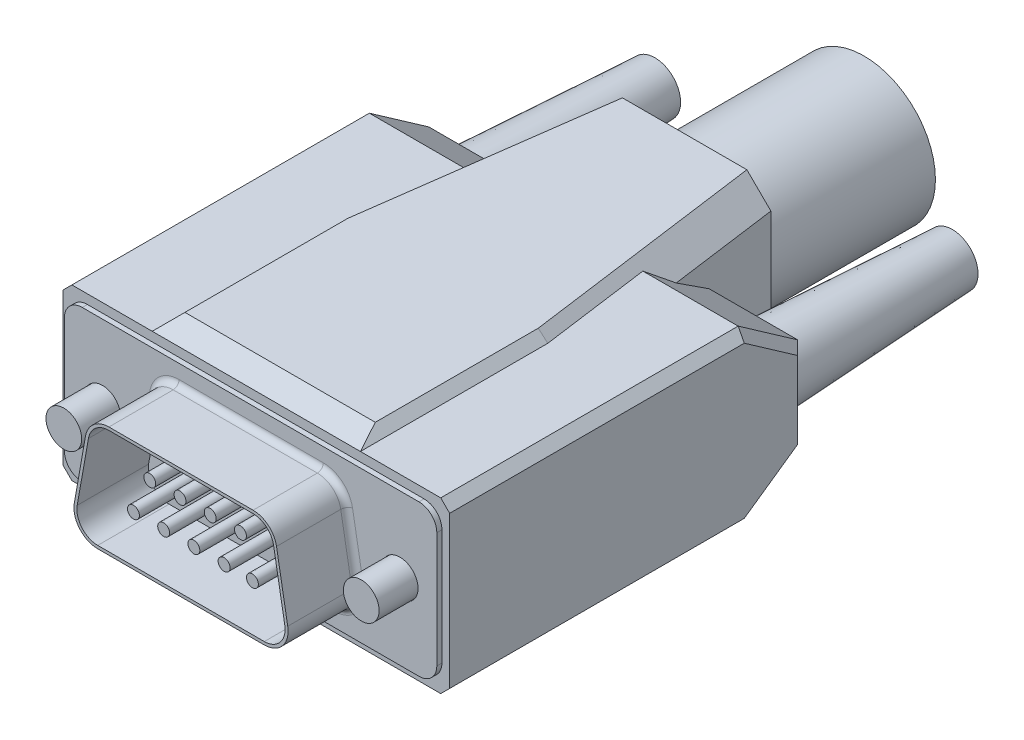
SolidWorks part; units mm, degrees
ref_plane "Plane1" through (0, 0, 0) normal (0, 0, 1) x (1, 0, 0)
ref_plane "Plane2" through (0, 0, 0) normal (0, 1, 0) x (1, 0, 0)
ref_plane "Plane3" through (0, 0, 0) normal (1, 0, 0) x (0, 0, -1)
other "Configuration Table"
sketch "Sketch1" plane through (0, 0, 0) normal (0, 0, 1) x (1, 0, 0)
  line L0 (-15.7, -6.35) -> (15.6, -6.35)
  line L1 (-15.7, -6.35) -> (-15.7, 6.35)
  line L2 (15.6, 6.35) -> (-15.7, 6.35)
  line L3 (15.6, 6.35) -> (15.6, -6.35)
  line L8 (-29.9573, 0) -> (30.1121, 0) construction
  line L9 (0, 20.0131) -> (0, -19.9874) construction
  circle A0 centre (12.5, 0) radius 1.525
  circle A1 centre (-12.5, 0) radius 1.525
  dimension "D10" = 3.05
  dimension "D1" = 12.7
  dimension "D2" = 31.3
  dimension "D5" = 12.5
  dimension "D6" = 15.6
  dimension "D7" = 6.35
extrude "Base-Extrude" add sketch "Sketch1" along normal mid plane 0.43
fillet "Fillet6" radius 1.5 4 edges at (15.6, 6.35, 0) (15.6, -6.35, 0) (-15.7, -6.35, 0) (-15.7, 6.35, 0)
sketch "Sketch4" plane through (0, 0, 0.215) normal (0, 0, 1) x (1, 0, 0)
  line L0 (20.0414, 0) -> (-20.2241, 0) construction
  line L1 (0, -10.1349) -> (0, 10.0435) construction
  line L2 (7, -4.67) -> (-7, -4.67)
  line L3 (-8.9696, -2.3227) -> (-8.028, 3.0173)
  line L4 (-6.0584, 4.67) -> (6.0584, 4.67)
  line L5 (8.9696, -2.3227) -> (8.028, 3.0173)
  arc A0 (-8.9696, -2.3227) -> (-7, -4.67) centre (-7, -2.67) ccw
  arc A1 (-6.0584, 4.67) -> (-8.028, 3.0173) centre (-6.0584, 2.67) ccw
  arc A2 (8.9696, -2.3227) -> (7, -4.67) centre (7, -2.67) cw
  arc A3 (6.0584, 4.67) -> (8.028, 3.0173) centre (6.0584, 2.67) cw
  point P15 (0, -4.67)
  point P18 (0, 4.67)
  dimension "D1" = 2
  dimension "D2" = 2
  dimension "D3" = 7
  dimension "D4" = 2.67
  dimension "D5" = 9.34
  dimension "D6" = 100
extrude "Boss-Extrude2" add sketch "Sketch4" along normal blind 5.9
fillet "Fillet8" radius 0.5 8 edges at (7.344, 4.2021, 0.215) (0, 4.67, 0.215) (8.4988, 0.3473, 0.215) (8.5321, -3.9556, 0.215) (0, -4.67, 0.215) (-8.5321, -3.9556, 0.215) (-8.4988, 0.3473, 0.215) (-7.344, 4.2021, 0.215)
sketch "Sketch5" plane through (0, 0, 6.115) normal (0, 0, 1) x (1, 0, 0)
  line L4 (-7, -4.42) -> (7, -4.42)
  line L5 (8.7234, -2.3661) -> (7.7818, 2.9739)
  line L6 (6.0584, 4.42) -> (-6.0584, 4.42)
  line L7 (-7.7818, 2.9739) -> (-8.7234, -2.3661)
  line L8 (-7, -4.42) -> (7, -4.42)
  line L9 (8.7234, -2.3661) -> (7.7818, 2.9739)
  line L10 (6.0584, 4.42) -> (-6.0584, 4.42)
  line L11 (-7.7818, 2.9739) -> (-8.7234, -2.3661)
  arc A4 (-8.7234, -2.3661) -> (-7, -4.42) centre (-7, -2.67) ccw
  arc A5 (7, -4.42) -> (8.7234, -2.3661) centre (7, -2.67) ccw
  arc A6 (7.7818, 2.9739) -> (6.0584, 4.42) centre (6.0584, 2.67) ccw
  arc A7 (-6.0584, 4.42) -> (-7.7818, 2.9739) centre (-6.0584, 2.67) ccw
  arc A8 (-8.7234, -2.3661) -> (-7, -4.42) centre (-7, -2.67) ccw
  arc A9 (7, -4.42) -> (8.7234, -2.3661) centre (7, -2.67) ccw
  arc A10 (7.7818, 2.9739) -> (6.0584, 4.42) centre (6.0584, 2.67) ccw
  arc A11 (-6.0584, 4.42) -> (-7.7818, 2.9739) centre (-6.0584, 2.67) ccw
  dimension "D1" = 0.25
extrude "Cut-Extrude1" cut sketch "Sketch5" against normal blind 6
sketch "Sketch8" plane through (0, 0, 0.115) normal (0, 0, 1) x (1, 0, 0)
  line L0 (-17.0623, 0) -> (18.229, 0) construction
  line L1 (0, 8.3424) -> (0, -9.7837) construction
  circle A0 centre (-5, -1.5) radius 0.5
  circle A1 centre (-3.625, 1.5) radius 0.5
  dimension "D1" = 1
  dimension "D4" = 3
  dimension "D3" = 1
  dimension "D2" = 5
  dimension "D5" = 1.375
  dimension "D6" = 1.5
extrude "Boss-Extrude3" add sketch "Sketch8" along normal blind 5
pattern_linear "LPattern1" count 4 spacing 2.54 along (1, 0, 0) of "Boss-Extrude3"
sketch "Sketch9" plane through (0, 0, -0.215) normal (0, 0, -1) x (-1, 0, 0)
  line L1 (-16.25, 7.125) -> (16.25, 7.125)
  line L2 (-16.25, 7.125) -> (-16.25, -7.125)
  line L3 (-16.25, -7.125) -> (16.25, -7.125)
  line L4 (16.25, 7.125) -> (16.25, -7.125)
  dimension "D1" = 32.5
  dimension "D2" = 14.25
  dimension "D3" = 7.125
  dimension "D4" = 16.25
extrude "Boss-Extrude4" add sketch "Sketch9" along normal blind 30
sketch "Sketch11" plane through (0, 0, -30.215) normal (0, 0, -1) x (-1, 0, 0)
  circle A0 centre (-12.5, 0) radius 2
  circle A1 centre (12.5, 0) radius 2
  dimension "D1" = 4
  dimension "D2" = 4
extrude "Cut-Extrude3" cut sketch "Sketch11" against normal blind 20
sketch "Sketch12" plane through (0, 0, -30.215) normal (0, 0, -1) x (-1, 0, 0)
  line L1 (-8.75, 7.875) -> (8.75, 7.875)
  line L2 (-8.75, 7.875) -> (-8.75, -7.875)
  line L3 (-8.75, -7.875) -> (8.75, -7.875)
  line L4 (8.75, 7.875) -> (8.75, -7.875)
  dimension "D1" = 17.5
  dimension "D2" = 15.75
  dimension "D3" = 8.75
  dimension "D4" = 7.875
extrude "Boss-Extrude6" add sketch "Sketch12" along normal blind 6 and the other way blind 30
chamfer "Chamfer1" distance 5 distance2 3.5 4 edges at (-12.5, 7.125, -30.215) (12.5, 7.125, -30.215) (-12.5, -7.125, -30.215) (12.5, -7.125, -30.215) first distance on face at (-12.5, 7.125, -15.215) first distance on face at (12.5, 7.125, -15.215) first distance on face at (-12.5, -7.125, -15.215) first distance on face at (12.5, -7.125, -15.215)
chamfer "Chamfer3" distance 11 distance2 1.5 2 edges at (-8.75, 0, -36.215) (8.75, 0, -36.215) first distance on face at (-8.75, 0, -18.415) first distance on face at (8.75, 0, -18.415)
chamfer "Chamfer4" distance 2 angle 45 4 edges at (8, 7.875, -30.715) (-8, 7.875, -30.715) (-8, -7.875, -30.715) (8, -7.875, -30.715)
chamfer "Chamfer6" distance 0.75 angle 45 14 edges at (16.25, 7.125, -12.715) (-16.25, 5.375, -27.715) (-16.25, 7.125, -12.715) (-16.25, -7.125, -12.715) (-16.25, -5.375, -27.715) (-16.25, 0, -30.215) (16.25, 0, -30.215) (16.25, -5.375, -27.715) (16.25, -7.125, -12.715) (16.25, 5.375, -27.715) (-8.75, 7.875, -5.3138) (8.75, 7.875, -5.3138) (-8.75, -7.875, -5.3138) (8.75, -7.875, -5.3138)
chamfer "Chamfer7" distance 0.75 distance2 2 2 edges at (0, 7.875, -0.215) (0, -7.875, -0.215) first distance on face at (-0.05, 0, -0.215)
sketch "Sketch18" plane through (0, 0, -36.215) normal (0, 0, -1) x (-1, 0, 0)
  circle A0 centre (0, 0) radius 6
  dimension "D1" = 12
extrude "Boss-Extrude8" add sketch "Sketch18" along normal blind 15.08
sketch "Sketch20" plane through (0, 0, 0.115) normal (0, 0, 1) x (1, 0, 0)
  circle A0 centre (5, -1.5) radius 0.5
  dimension "D1" = 1
  dimension "D2" = 5
  dimension "D3" = 1.5
extrude "Boss-Extrude10" add sketch "Sketch20" along normal blind 5
sketch "Sketch21" plane through (0, 0, 0.215) normal (0, 0, 1) x (1, 0, 0)
  circle A0 centre (-12.5, 0) radius 1.5
  circle A1 centre (12.5, 0) radius 1.5
  dimension "D1" = 3
  dimension "D2" = 3
sketch "Sketch22" plane through (0, 0, -30.215) normal (0, 0, -1) x (-1, 0, 0)
  circle A0 centre (12.5, 0) radius 2
  circle A1 centre (-12.5, 0) radius 2
  dimension "D1" = 4
  dimension "D2" = 4
extrude "Boss-Extrude12" add sketch "Sketch22" along normal blind 2 and the other way up to surface (20 mm away) other way up to face at (10.5, 0, -10.215)
extrude "Boss-Extrude14" add sketch "Sketch21" along normal blind 3.25 and the other way up to next
sketch "Sketch23" plane through (0, 0, -30.215) normal (0, 0, -1) x (-1, 0, 0)
  circle A0 centre (12.5, 0) radius 3
  circle A1 centre (-12.5, 0) radius 3
  dimension "D1" = 6
  dimension "D2" = 6
extrude "Boss-Extrude15" add sketch "Sketch23" along normal blind 16 draft 3
sketch "Sketch24" plane through (0, 0, -51.295) normal (0, 0, -1) x (-1, 0, 0)
  circle A1 centre (0, 0) radius 6 construction
  point P0 (0, 0)
  point P1 (0, 0)
other "CPoint1" parameters "Diameter"=5, "StubLength"=0
ref_axis "Axis1" through (0, 0, -61.295) along (0, 0, 1)
